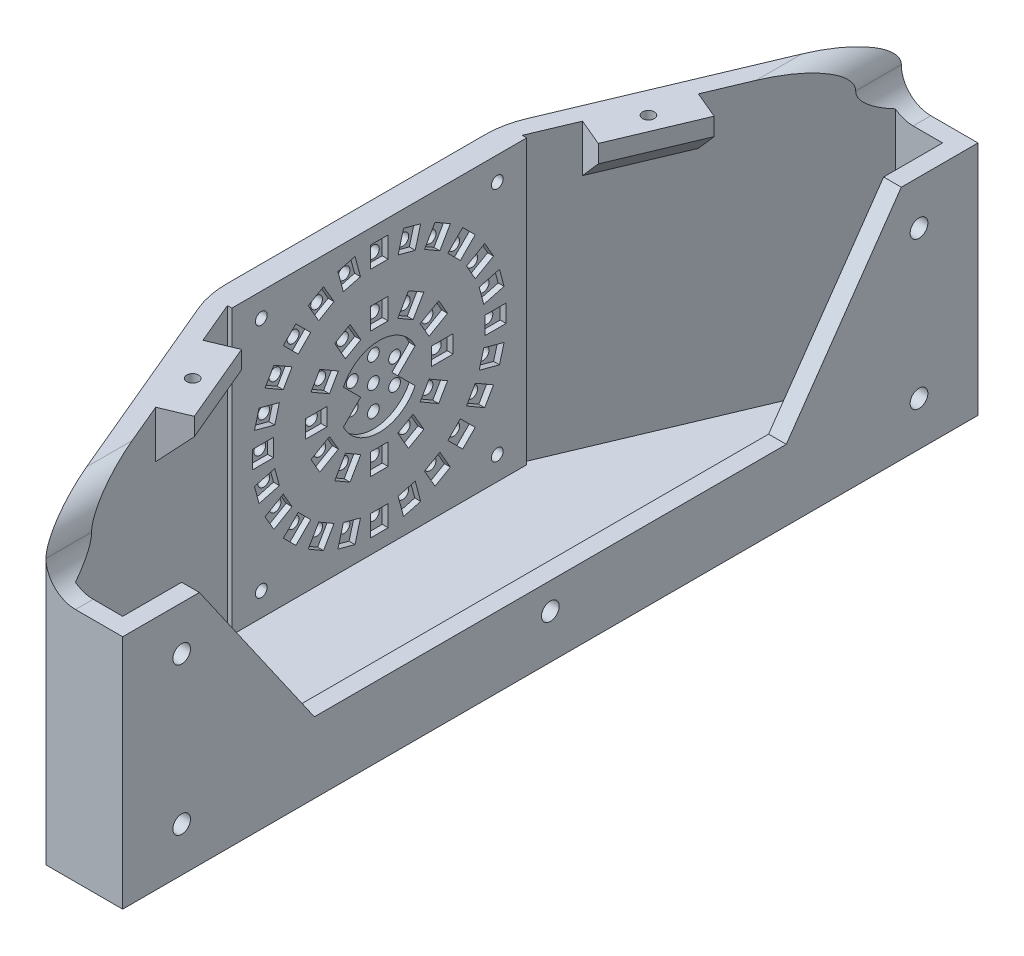
SolidWorks part; units mm, degrees
ref_plane "Спереди" through (0, 0, 0) normal (0, 0, 1) x (1, 0, 0)
ref_plane "Сверху" through (0, 0, 0) normal (0, 1, 0) x (1, 0, 0)
ref_plane "Справа" through (0, 0, 0) normal (1, 0, 0) x (0, 0, -1)
sketch "Эскиз1" plane through (0, 0, 0) normal (0, 1, 0) x (1, 0, 0)
  line L0 (0, 159.887) -> (0, 0) construction
  line L1 (0, 0) -> (281.7797, 0) construction
  line L2 (-50, -50) -> (-50, 50)
  line L3 (-10, -145) -> (10, -145)
  line L5 (-10, 145) -> (10, 145)
  line L6 (10, -145) -> (10, 145)
  line L7 (0, 145) -> (0, -145) construction
  line L8 (-435.8276, 0) -> (10, 0) construction
  line L9 (-50, 50) -> (-10, 145)
  line L10 (-50, -50) -> (-10, -145)
  point P10 (-50, 0)
  dimension "D1" = 290
  dimension "D2" = 20
  dimension "D3" = 100
  dimension "D4" = 60
extrude "Бобышка-Вытянуть1" add sketch "Эскиз1" along normal blind 4
sketch "Эскиз2" plane through (0, 0, 0) normal (0, 1, 0) x (1, 0, 0)
  line L1 (10, 145) -> (16, 145)
  line L2 (10, 145) -> (10, -145)
  line L3 (10, -145) -> (16, -145)
  line L4 (16, 145) -> (16, -145)
  dimension "D1" = 290
  dimension "D2" = 6
extrude "Бобышка-Вытянуть2" add sketch "Эскиз2" along normal blind 80
sketch "Эскиз17" plane through (0, 4, 0) normal (0, 1, 0) x (1, 0, 0)
  line L0 (-10, 145) -> (-50, 50)
  line L1 (-50, 50) -> (-50, -50)
  line L2 (-50, -50) -> (-10, -145)
  line L3 (-10, -145) -> (16, -145)
  line L4 (16, -145) -> (16, 145)
  line L5 (16, 145) -> (-10, 145)
extrude "Вытянуть-Тонкостенный1" add sketch "Эскиз17" along normal blind 96 thin thin type one direction reverse wall 6
sketch "Эскиз29" plane through (0, 100, 0) normal (0, 1, 0) x (1, 0, 0)
  line L1 (-50, 50) -> (-42, 50)
  line L2 (-50, 50) -> (-50, -50)
  line L3 (-50, -50) -> (-42, -50)
  line L4 (-42, 50) -> (-42, -50)
  dimension "D1" = 8
extrude "Бобышка-Вытянуть5" add sketch "Эскиз29" against normal blind 96
sketch "Эскиз20" plane through (-42, 0, 0) normal (1, 0, 0) x (0, 0, -1)
  line L0 (8.2314, 94.3113) -> (6.3873, 87.4288)
  line L1 (6.3, 52) -> (12.1612, 57.8612)
  line L10 (0, 0) -> (0, 100) construction
  line L12 (-48.7884, 52) -> (48.7884, 52) construction
  line L15 (-3, 95) -> (3, 95)
  line L16 (-3, 95) -> (-3, 87.8748)
  line L17 (-3, 87.8748) -> (3, 87.8748)
  line L18 (3, 95) -> (3, 87.8748)
  line L19 (0, 87.8748) -> (0, 95) construction
  line L20 (-3, 91.4374) -> (3, 91.4374) construction
  line L21 (8.2314, 94.3113) -> (14.027, 92.7584)
  line L22 (14.027, 92.7584) -> (12.1829, 85.8759)
  line L23 (6.3873, 87.4288) -> (12.1829, 85.8759)
  line L24 (18.9019, 90.7391) -> (15.3393, 84.5685)
  line L25 (18.9019, 90.7391) -> (24.0981, 87.7391)
  line L26 (24.0981, 87.7391) -> (20.5355, 81.5685)
  line L27 (15.3393, 84.5685) -> (20.5355, 81.5685)
  line L28 (28.2843, 84.5269) -> (23.246, 79.4886)
  line L29 (28.2843, 84.5269) -> (32.5269, 80.2843)
  line L30 (32.5269, 80.2843) -> (27.4886, 75.246)
  line L31 (23.246, 79.4886) -> (27.4886, 75.246)
  line L32 (35.7391, 76.0981) -> (29.5685, 72.5355)
  line L33 (35.7391, 76.0981) -> (38.7391, 70.9019)
  line L34 (38.7391, 70.9019) -> (32.5685, 67.3393)
  line L35 (29.5685, 72.5355) -> (32.5685, 67.3393)
  line L36 (40.7584, 66.027) -> (33.8759, 64.1829)
  line L37 (40.7584, 66.027) -> (42.3113, 60.2314)
  line L38 (42.3113, 60.2314) -> (35.4288, 58.3873)
  line L39 (33.8759, 64.1829) -> (35.4288, 58.3873)
  line L40 (43, 55) -> (35.8748, 55)
  line L41 (43, 55) -> (43, 49)
  line L42 (43, 49) -> (35.8748, 49)
  line L43 (35.8748, 55) -> (35.8748, 49)
  line L44 (42.3113, 43.7686) -> (35.4288, 45.6127)
  line L45 (42.3113, 43.7686) -> (40.7584, 37.973)
  line L46 (40.7584, 37.973) -> (33.8759, 39.8171)
  line L47 (35.4288, 45.6127) -> (33.8759, 39.8171)
  line L48 (38.7391, 33.0981) -> (32.5685, 36.6607)
  line L49 (38.7391, 33.0981) -> (35.7391, 27.9019)
  line L50 (35.7391, 27.9019) -> (29.5685, 31.4645)
  line L51 (32.5685, 36.6607) -> (29.5685, 31.4645)
  line L52 (32.5269, 23.7157) -> (27.4886, 28.754)
  line L53 (32.5269, 23.7157) -> (28.2843, 19.4731)
  line L54 (28.2843, 19.4731) -> (23.246, 24.5114)
  line L55 (27.4886, 28.754) -> (23.246, 24.5114)
  line L56 (24.0981, 16.2609) -> (20.5355, 22.4315)
  line L57 (24.0981, 16.2609) -> (18.9019, 13.2609)
  line L58 (18.9019, 13.2609) -> (15.3393, 19.4315)
  line L59 (20.5355, 22.4315) -> (15.3393, 19.4315)
  line L60 (14.027, 11.2416) -> (12.1829, 18.1241)
  line L61 (14.027, 11.2416) -> (8.2314, 9.6887)
  line L62 (8.2314, 9.6887) -> (6.3873, 16.5712)
  line L63 (12.1829, 18.1241) -> (6.3873, 16.5712)
  line L64 (3, 9) -> (3, 16.1252)
  line L65 (3, 9) -> (-3, 9)
  line L66 (-3, 9) -> (-3, 16.1252)
  line L67 (3, 16.1252) -> (-3, 16.1252)
  line L68 (-8.2314, 9.6887) -> (-6.3873, 16.5712)
  line L69 (-8.2314, 9.6887) -> (-14.027, 11.2416)
  line L70 (-14.027, 11.2416) -> (-12.1829, 18.1241)
  line L71 (-6.3873, 16.5712) -> (-12.1829, 18.1241)
  line L72 (-18.9019, 13.2609) -> (-15.3393, 19.4315)
  line L73 (-18.9019, 13.2609) -> (-24.0981, 16.2609)
  line L74 (-24.0981, 16.2609) -> (-20.5355, 22.4315)
  line L75 (-15.3393, 19.4315) -> (-20.5355, 22.4315)
  line L76 (-28.2843, 19.4731) -> (-23.246, 24.5114)
  line L77 (-28.2843, 19.4731) -> (-32.5269, 23.7157)
  line L78 (-32.5269, 23.7157) -> (-27.4886, 28.754)
  line L79 (-23.246, 24.5114) -> (-27.4886, 28.754)
  line L80 (-35.7391, 27.9019) -> (-29.5685, 31.4645)
  line L81 (-35.7391, 27.9019) -> (-38.7391, 33.0981)
  line L82 (-38.7391, 33.0981) -> (-32.5685, 36.6607)
  line L83 (-29.5685, 31.4645) -> (-32.5685, 36.6607)
  line L84 (-40.7584, 37.973) -> (-33.8759, 39.8171)
  line L85 (-40.7584, 37.973) -> (-42.3113, 43.7686)
  line L86 (-42.3113, 43.7686) -> (-35.4288, 45.6127)
  line L87 (-33.8759, 39.8171) -> (-35.4288, 45.6127)
  line L88 (-43, 49) -> (-35.8748, 49)
  line L89 (-43, 49) -> (-43, 55)
  line L90 (-43, 55) -> (-35.8748, 55)
  line L91 (-35.8748, 49) -> (-35.8748, 55)
  line L92 (-42.3113, 60.2314) -> (-35.4288, 58.3873)
  line L93 (-42.3113, 60.2314) -> (-40.7584, 66.027)
  line L94 (-40.7584, 66.027) -> (-33.8759, 64.1829)
  line L95 (-35.4288, 58.3873) -> (-33.8759, 64.1829)
  line L96 (-38.7391, 70.9019) -> (-32.5685, 67.3393)
  line L97 (-38.7391, 70.9019) -> (-35.7391, 76.0981)
  line L98 (-35.7391, 76.0981) -> (-29.5685, 72.5355)
  line L99 (-32.5685, 67.3393) -> (-29.5685, 72.5355)
  line L100 (-32.5269, 80.2843) -> (-27.4886, 75.246)
  line L101 (-32.5269, 80.2843) -> (-28.2843, 84.5269)
  line L102 (-28.2843, 84.5269) -> (-23.246, 79.4886)
  line L103 (-27.4886, 75.246) -> (-23.246, 79.4886)
  line L104 (-24.0981, 87.7391) -> (-20.5355, 81.5685)
  line L105 (-24.0981, 87.7391) -> (-18.9019, 90.7391)
  line L106 (-18.9019, 90.7391) -> (-15.3393, 84.5685)
  line L107 (-20.5355, 81.5685) -> (-15.3393, 84.5685)
  line L108 (-14.027, 92.7584) -> (-12.1829, 85.8759)
  line L109 (-14.027, 92.7584) -> (-8.2314, 94.3113)
  line L110 (-8.2314, 94.3113) -> (-6.3873, 87.4288)
  line L111 (-12.1829, 85.8759) -> (-6.3873, 87.4288)
  line L112 (6.276, 68.8704) -> (9.9019, 75.1506)
  line L113 (-3, 69.7482) -> (3, 69.7482)
  line L114 (-3, 69.7482) -> (-3, 77)
  line L115 (-3, 77) -> (3, 77)
  line L116 (3, 69.7482) -> (3, 77)
  line L117 (0, 77) -> (0, 69.7482) construction
  line L118 (-3, 73.3741) -> (3, 73.3741) construction
  line L119 (6.276, 68.8704) -> (11.4722, 65.8704)
  line L120 (11.4722, 65.8704) -> (15.0981, 72.1506)
  line L121 (9.9019, 75.1506) -> (15.0981, 72.1506)
  line L122 (13.8704, 63.4722) -> (20.1506, 67.0981)
  line L123 (13.8704, 63.4722) -> (16.8704, 58.276)
  line L124 (16.8704, 58.276) -> (23.1506, 61.9019)
  line L125 (20.1506, 67.0981) -> (23.1506, 61.9019)
  line L126 (17.7482, 55) -> (25, 55)
  line L127 (17.7482, 55) -> (17.7482, 49)
  line L128 (17.7482, 49) -> (25, 49)
  line L129 (25, 55) -> (25, 49)
  line L130 (16.8704, 45.724) -> (23.1506, 42.0981)
  line L131 (16.8704, 45.724) -> (13.8704, 40.5278)
  line L132 (13.8704, 40.5278) -> (20.1506, 36.9019)
  line L133 (23.1506, 42.0981) -> (20.1506, 36.9019)
  line L134 (11.4722, 38.1296) -> (15.0981, 31.8494)
  line L135 (11.4722, 38.1296) -> (6.276, 35.1296)
  line L136 (6.276, 35.1296) -> (9.9019, 28.8494)
  line L137 (15.0981, 31.8494) -> (9.9019, 28.8494)
  line L138 (3, 34.2518) -> (3, 27)
  line L139 (3, 34.2518) -> (-3, 34.2518)
  line L140 (-3, 34.2518) -> (-3, 27)
  line L141 (3, 27) -> (-3, 27)
  line L142 (-6.276, 35.1296) -> (-9.9019, 28.8494)
  line L143 (-6.276, 35.1296) -> (-11.4722, 38.1296)
  line L144 (-11.4722, 38.1296) -> (-15.0981, 31.8494)
  line L145 (-9.9019, 28.8494) -> (-15.0981, 31.8494)
  line L146 (-13.8704, 40.5278) -> (-20.1506, 36.9019)
  line L147 (-13.8704, 40.5278) -> (-16.8704, 45.724)
  line L148 (-16.8704, 45.724) -> (-23.1506, 42.0981)
  line L149 (-20.1506, 36.9019) -> (-23.1506, 42.0981)
  line L150 (-17.7482, 49) -> (-25, 49)
  line L151 (-17.7482, 49) -> (-17.7482, 55)
  line L152 (-17.7482, 55) -> (-25, 55)
  line L153 (-25, 49) -> (-25, 55)
  line L154 (-16.8704, 58.276) -> (-23.1506, 61.9019)
  line L155 (-16.8704, 58.276) -> (-13.8704, 63.4722)
  line L156 (-13.8704, 63.4722) -> (-20.1506, 67.0981)
  line L157 (-23.1506, 61.9019) -> (-20.1506, 67.0981)
  line L158 (-11.4722, 65.8704) -> (-15.0981, 72.1506)
  line L159 (-11.4722, 65.8704) -> (-6.276, 68.8704)
  line L160 (-6.276, 68.8704) -> (-9.9019, 75.1506)
  line L161 (-15.0981, 72.1506) -> (-9.9019, 75.1506)
  line L162 (6.3, 52) -> (12.1612, 46.1388)
  line L163 (-6.3, 52) -> (-12.1612, 57.8612)
  line L164 (-6.3, 52) -> (-12.1612, 46.1388)
  circle A0 centre (0, 52) radius 36 construction
  circle A1 centre (0, 52) radius 43 construction
  circle A3 centre (0, 52) radius 25 construction
  circle A4 centre (0, 52) radius 18 construction
  circle A5 centre (0, 52) radius 13.5 construction
  arc A6 (-12.1612, 57.8612) -> (12.1612, 57.8612) centre (0, 52) cw
  arc A7 (-12.1612, 46.1388) -> (12.1612, 46.1388) centre (0, 52) ccw
  point P15 (0, 91.4374)
  point P21 (0, 73.3741)
  point P112 (0, 52)
  point P163 (0, 52)
  dimension "D1" = 72
  dimension "D2" = 86
  dimension "D3" = 50
  dimension "D5" = 36
  dimension "D7" = 27
  dimension "D4" = 6
  dimension "D6" = 6
  dimension "D8" = 6.3
  dimension "D9" = 90
extrude "Вырез-Вытянуть7" cut sketch "Эскиз20" against normal blind 2
sketch "Эскиз16" plane through (16, 0, 0) normal (1, 0, 0) x (0, 0, -1)
  line L0 (0, 111.0778) -> (0, 40) construction
  line L1 (0, 40) -> (205.7417, 40) construction
  line L2 (-145, 0) -> (145, 0) construction
  circle A0 centre (0, 65) radius 3
  circle A1 centre (0, 15) radius 3
  circle A2 centre (125, 65) radius 3
  circle A3 centre (-125, 65) radius 3
  circle A4 centre (-125, 15) radius 3
  circle A5 centre (125, 15) radius 3
  dimension "D2" = 6
  dimension "D3" = 25
  dimension "D4" = 125
  dimension "D1" = 40
extrude "Вырез-Вытянуть6" cut sketch "Эскиз16" against normal blind 20
sketch "Эскиз21" plane through (-42, 0, 0) normal (1, 0, 0) x (0, 0, -1)
  line L0 (48.7884, 52) -> (-48.7884, 52) construction
  line L3 (0, 100) -> (0, 0) construction
  circle A0 centre (0, 52) radius 38.5 construction
  circle A1 centre (0, 90.5) radius 2
  circle A2 centre (9.9645, 89.1881) radius 2
  circle A3 centre (19.25, 85.342) radius 2
  circle A4 centre (27.2236, 79.2236) radius 2
  circle A5 centre (33.342, 71.25) radius 2
  circle A6 centre (37.1881, 61.9645) radius 2
  circle A7 centre (38.5, 52) radius 2
  circle A8 centre (37.1881, 42.0355) radius 2
  circle A9 centre (33.342, 32.75) radius 2
  circle A10 centre (27.2236, 24.7764) radius 2
  circle A11 centre (19.25, 18.658) radius 2
  circle A12 centre (9.9645, 14.8119) radius 2
  circle A13 centre (0, 13.5) radius 2
  circle A14 centre (-9.9645, 14.8119) radius 2
  circle A15 centre (-19.25, 18.658) radius 2
  circle A16 centre (-27.2236, 24.7764) radius 2
  circle A17 centre (-33.342, 32.75) radius 2
  circle A18 centre (-37.1881, 42.0355) radius 2
  circle A19 centre (-38.5, 52) radius 2
  circle A20 centre (-37.1881, 61.9645) radius 2
  circle A21 centre (-33.342, 71.25) radius 2
  circle A22 centre (-27.2236, 79.2236) radius 2
  circle A23 centre (-19.25, 85.342) radius 2
  circle A24 centre (-9.9645, 89.1881) radius 2
  circle A25 centre (0, 52) radius 21 construction
  circle A26 centre (0, 73) radius 2
  circle A27 centre (10.5, 70.1865) radius 2
  circle A28 centre (18.1865, 62.5) radius 2
  circle A29 centre (21, 52) radius 2
  circle A30 centre (18.1865, 41.5) radius 2
  circle A31 centre (10.5, 33.8135) radius 2
  circle A32 centre (0, 31) radius 2
  circle A33 centre (-10.5, 33.8135) radius 2
  circle A34 centre (-18.1865, 41.5) radius 2
  circle A35 centre (-21, 52) radius 2
  circle A36 centre (-18.1865, 62.5) radius 2
  circle A37 centre (-10.5, 70.1865) radius 2
  circle A38 centre (0, 52) radius 8.3 construction
  circle A39 centre (0, 60.3) radius 2
  circle A40 centre (7.188, 56.15) radius 2
  circle A41 centre (7.188, 47.85) radius 2
  circle A42 centre (0, 43.7) radius 2
  circle A43 centre (-7.188, 47.85) radius 2
  circle A44 centre (-7.188, 56.15) radius 2
  circle A45 centre (0, 52) radius 2
  point P64 (0, 52)
  point P90 (0, 52)
  point P104 (0, 52)
  dimension "D1" = 77
  dimension "D2" = 4
  dimension "D3" = 42
  dimension "D4" = 4
  dimension "D5" = 16.6
  dimension "D6" = 4
extrude "Отверстия под LED" cut sketch "Эскиз21" against normal blind 10
sketch "Эскиз22" plane through (0, 100, 0) normal (0, 1, 0) x (1, 0, 0)
  line L1 (16, 145) -> (-10, 145)
  line L2 (16, 145) -> (16, -145)
  line L3 (16, -145) -> (-10, -145)
  line L4 (-10, 145) -> (-10, -145)
extrude "Вырез-Вытянуть9" cut sketch "Эскиз22" against normal blind 20
fillet "Скругление2" radius 10 4 edges at (-10, 100, -137.2692) (-10, 100, 137.2692) (-10, 80, -137.2692) (-10, 80, 137.2692)
fillet "Скругление3" radius 30 2 edges at (-50, 50, 50) (-50, 50, -50)
sketch "Эскиз23" plane through (-54.8231, 0, -23.0834) normal (0.9216, 0, 0.3881) x (0.3881, 0, -0.9216)
  line L0 (89.7371, 100) -> (29.2052, 100) construction
  line L1 (44.7834, 100) -> (74.7834, 100)
  line L2 (44.7834, 100) -> (44.7834, 94)
  line L3 (44.7834, 94) -> (74.7834, 94)
  line L4 (74.7834, 100) -> (74.7834, 94)
  line L6 (29.7834, 4) -> (29.7834, 100) construction
  dimension "D1" = 30
  dimension "D2" = 6
  dimension "D3" = 15
extrude "Бобышка-Вытянуть3" add sketch "Эскиз23" along normal blind 10
sketch "Эскиз24" plane through (-54.8231, 0, 23.0834) normal (0.9216, 0, -0.3881) x (-0.3881, 0, -0.9216)
  line L0 (-29.2052, 100) -> (-89.7371, 100) construction
  line L1 (-44.7834, 100) -> (-74.7834, 100)
  line L2 (-44.7834, 100) -> (-44.7834, 94)
  line L3 (-44.7834, 94) -> (-74.7834, 94)
  line L4 (-74.7834, 100) -> (-74.7834, 94)
  line L6 (-29.7834, 4) -> (-29.7834, 100) construction
  dimension "D1" = 30
  dimension "D2" = 6
  dimension "D3" = 15
extrude "Бобышка-Вытянуть4" add sketch "Эскиз24" along normal blind 10
chamfer "Фаска1" distance 10 angle 45 2 edges at (-31.6238, 94, -78.1819) (-31.6238, 94, 78.1819)
sketch "Эскиз27" plane through (16, 0, 0) normal (1, 0, 0) x (0, 0, -1)
  line L0 (-80, 24) -> (80, 24)
  line L1 (80, 24) -> (119, 80)
  line L2 (-145, 80) -> (145, 80) construction
  line L3 (119, 80) -> (-119, 80)
  line L4 (0, 118.8906) -> (0, 0) construction
  line L5 (-80, 24) -> (-119, 80)
  line L6 (-145, 0) -> (145, 0) construction
  line L7 (145, 80) -> (145, 0) construction
  point P10 (0, 80)
  point P11 (0, 24)
  dimension "D1" = 160
  dimension "D2" = 24
  dimension "D3" = 26
extrude "Вырез-Вытянуть10" cut sketch "Эскиз27" against normal blind 10
chamfer "Фаска2" distance 2 angle 45 24 edges at (-50, 71.25, 31.342) (-50, 61.9645, 35.1881) (-50, 52, 36.5) (-50, 42.0355, 35.1881) (-50, 32.75, 31.342) (-50, 24.7764, 25.2236) (-50, 18.658, 17.25) (-50, 14.8119, 7.9645) (-50, 13.5, -2) (-50, 14.8119, -11.9645) (-50, 18.658, -21.25) (-50, 24.7764, -29.2236) (-50, 32.75, -35.342) (-50, 42.0355, -39.1881) (-50, 52, -40.5) (-50, 61.9645, -39.1881) (-50, 71.25, -35.342) (-50, 79.2236, -29.2236) (-50, 85.342, -21.25) (-50, 89.1881, -11.9645) (-50, 90.5, -2) (-50, 79.2236, 25.2236) (-50, 85.342, 17.25) (-50, 89.1881, 7.9645)
sketch "Эскиз30" plane through (-42, 0, 0) normal (1, 0, 0) x (0, 0, -1)
  line L1 (-40, 12) -> (40, 12) construction
  line L2 (-40, 12) -> (-40, 92) construction
  line L3 (-40, 92) -> (40, 92) construction
  line L4 (40, 12) -> (40, 92) construction
  line L5 (0, 92) -> (0, 12) construction
  line L6 (-40, 52) -> (40, 52) construction
  circle A0 centre (-40, 92) radius 2
  circle A1 centre (40, 92) radius 2
  circle A2 centre (-40, 12) radius 2
  circle A3 centre (40, 12) radius 2
  point P0 (0, 52)
  dimension "D1" = 80
  dimension "D2" = 80
extrude "Вырез-Вытянуть11" cut sketch "Эскиз30" against normal blind 7
sketch "Эскиз32" plane through (0, 100, 0) normal (0, 1, 0) x (1, 0, 0)
  line L0 (-28, 139.8441) -> (-28, -154.1375) construction
  line L1 (-50, 43.9418) -> (-50, -43.9418) construction
  line L2 (0, 0) -> (-175.2904, 0) construction
  circle A0 centre (-28, 77.2619) radius 2
  circle A1 centre (-28, -77.2619) radius 2
  dimension "D2" = 77.2619
  dimension "D1" = 22
extrude "Вырез-Вытянуть13" cut sketch "Эскиз32" against normal blind 7
chamfer "Фаска3" distance 2 angle 45 7 edges at (-50, 47.85, 5.188) (-50, 43.7, -2) (-50, 47.85, -9.188) (-50, 56.15, -9.188) (-50, 52, -2) (-50, 56.15, 5.188) (-50, 60.3, -2)
chamfer "Фаска4" distance 2 angle 45 12 edges at (-50, 52, 19) (-50, 41.5, 16.1865) (-50, 33.8135, 8.5) (-50, 31, -2) (-50, 33.8135, -12.5) (-50, 41.5, -20.1865) (-50, 52, -23) (-50, 62.5, -20.1865) (-50, 70.1865, -12.5) (-50, 73, -2) (-50, 70.1865, 8.5) (-50, 62.5, 16.1865)
